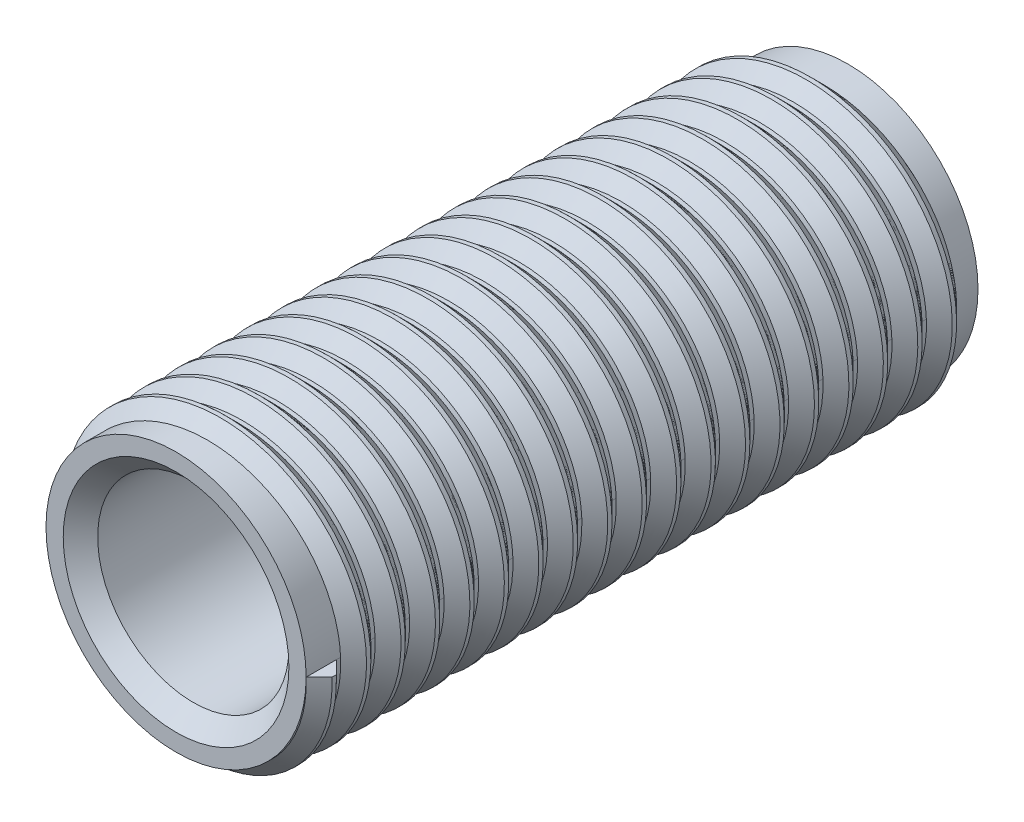
SolidWorks part; units mm, degrees
ref_plane "前视基准面" through (0, 0, 0) normal (0, 0, 1) x (1, 0, 0)
ref_plane "上视基准面" through (0, 0, 0) normal (0, 1, 0) x (1, 0, 0)
ref_plane "右视基准面" through (0, 0, 0) normal (1, 0, 0) x (0, 0, -1)
sketch "草图1" plane through (0, 0, 0) normal (0, 0, 1) x (1, 0, 0)
  circle A0 centre (0, 0) radius 15.1
  dimension "D1" = 30.2
extrude "凸台-拉伸1" add sketch "草图1" along normal blind 78 contours A0
ref_plane "基准面1" through (0, 0, 76.25) normal (0, 0, 1) x (1, 0, 0)
sketch "草图2" plane through (0, 0, 76.25) normal (0, 0, 1) x (1, 0, 0)
  circle A0 centre (0, 0) radius 15.1 construction
  circle A1 centre (0, 0) radius 15.1
curve "螺旋线/涡状线1" pitch 4 height 74 radius 15.1 centre (0, 0, 76.25) axis (0, 0, -1) start towards (1, 0, 0)
sketch "草图3" plane through (0, 0, 0) normal (0, 1, 0) x (1, 0, 0)
  line L0 (15.1, -74.5) -> (15.1, -78)
  line L1 (15.1, -78) -> (16.6, -76.5)
  line L2 (16.6, -76.5) -> (16.6, -76)
  line L3 (16.6, -76) -> (15.1, -74.5)
  point P2 (15.1, -76.25)
  dimension "D1" = 3.5
  dimension "D3" = 45
  dimension "D4" = 1.5
sweep "扫描1" add profiles "草图3" path "螺旋线/涡状线1"
sketch "草图4" plane through (0, 0, 78) normal (0, 0, 1) x (1, 0, 0)
  circle A0 centre (0, 0) radius 11.1
  circle A1 centre (0, 0) radius 15.1 construction
  dimension "D1" = 4
extrude "中孔" cut sketch "草图4" against normal through all contours A0
sketch "草图8" plane through (0, 0, 0) normal (0, 1, 0) x (1, 0, 0)
  line L0 (-11.1, 0) -> (-11.1, -78) construction
  line L1 (-11.1, -76) -> (-11.1, -78)
  line L4 (-11.1, -76) -> (-13.1, -78)
  line L5 (-15.1, -78) -> (15.1, -78) construction
  line L6 (-13.1, -78) -> (-11.1, -78)
  line L7 (0, 0) -> (0, 50000) construction
  dimension "D1" = 2
  dimension "D2" = 2
revolve "切除-旋转1" cut sketch "草图8" angle 360 about L7
ref_plane "基准面3" through (0, 0, 74.25) normal (0, 0, 1) x (1, 0, 0)
sketch "草图9" plane through (0, 0, 74.25) normal (0, 0, 1) x (1, 0, 0)
  circle A0 centre (0, 0) radius 11.1 construction
  circle A1 centre (0, 0) radius 11.1
ref_plane "基准面4" through (0, 0, 63) normal (0, 0, 1) x (1, 0, 0)
sketch "草图11" plane through (0, 0, 0) normal (0, 1, 0) x (1, 0, 0)
  line L0 (-11.1, 0) -> (-13.1, 0)
  line L3 (0, 0) -> (0, -2.5052) construction
  line L4 (-11.1, 0) -> (-11.1, -2)
  line L5 (-11.1, -2) -> (-13.1, 0)
  dimension "D1" = 2
  dimension "D2" = 2
revolve "切除-旋转2" cut sketch "草图11" angle 360 about L3
